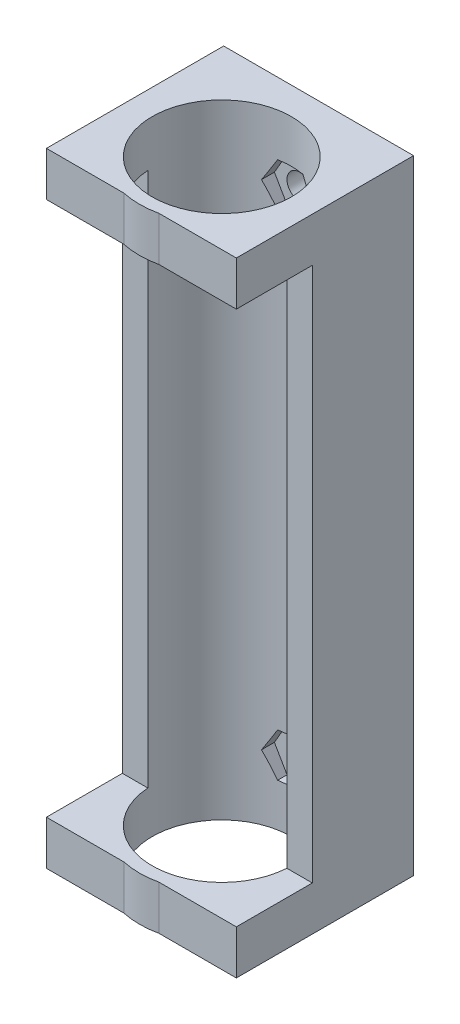
SolidWorks part; units mm, degrees
note: The reader was unsure of these and kept them because the rebuilt part matched: shared geometry of "Sketch2<2>", "Sketch2<3>", "Sketch1<6>", "Sketch1<7>".
material "ABS"
ref_plane "Front Plane" through (0, 0, 0) normal (0, 0, 1) x (1, 0, 0)
ref_plane "Top Plane" through (0, 0, 0) normal (0, 1, 0) x (1, 0, 0)
ref_plane "Right Plane" through (0, 0, 0) normal (1, 0, 0) x (0, 0, -1)
sketch "Sketch1" plane through (0, 0, 0) normal (0, 0, 1) x (1, 0, 0)
  line L0 (-315, -150.75) -> (-345, -150.75)
  line L1 (-315, -150.75) -> (-315, -249.25)
  line L2 (-345, -150.75) -> (-345, -249.25)
  line L3 (-315, -249.25) -> (-345, -249.25)
  line L4 (-343, -150.75) -> (-318.4975, -150.75) construction
  line L5 (-318.4975, -249.25) -> (-343, -249.25) construction
  line L7 (-326.0163, -161) -> (-328.0081, -157.55)
  line L8 (-328.0081, -157.55) -> (-331.9919, -157.55)
  line L9 (-331.9919, -157.55) -> (-333.9837, -161)
  line L10 (-333.9837, -161) -> (-331.9919, -164.45)
  line L11 (-331.9919, -164.45) -> (-328.0081, -164.45)
  line L12 (-328.0081, -164.45) -> (-326.0163, -161)
  line L13 (-333.9837, -239) -> (-331.9919, -242.45)
  line L14 (-331.9919, -242.45) -> (-328.0081, -242.45)
  line L15 (-328.0081, -242.45) -> (-326.0163, -239)
  line L16 (-326.0163, -239) -> (-328.0081, -235.55)
  line L17 (-328.0081, -235.55) -> (-331.9919, -235.55)
  line L18 (-331.9919, -235.55) -> (-333.9837, -239)
  circle A0 centre (-330, -161) radius 2 construction
  circle A1 centre (-330, -161) radius 2
  circle A2 centre (-330, -239) radius 2
  circle A3 centre (-330, -161) radius 3.45 construction
  circle A4 centre (-330, -239) radius 3.45 construction
  dimension "D1" = 15
  dimension "D2" = 15
  dimension "D3" = 0
  dimension "D4" = 0
  dimension "D5" = 6.9
  dimension "D6" = 6.9
sketch "Sketch2" plane through (0, -150.75, 0) normal (0, -1, 0) x (1, 0, 0)
  circle A0 centre (-330, 15.3006) radius 11
  circle A1 centre (-330, 15.3006) radius 13
  dimension "D1" = 22
  dimension "D2" = 26
extrude "Boss-Extrude3" add sketch "Sketch2" along normal up to surface (98.5 mm away)
extrude "Cut-Extrude2" cut sketch "Sketch2<2>" along normal offset from surface (84.5 mm away) 7 from offset 7
sketch "Sketch2<2>" plane through (0, -150.75, 0) normal (0, -1, 0) x (1, 0, 0) same geometry as "Sketch2"
extrude "Boss-Extrude5" add sketch "Sketch1" along normal blind 4 contours L3 L1 L0 L2 L18 L17 L16 L15 L14 L13 L12 L11 L10 L9 L8 L7 | L11 L12 L7 L8 L9 L10 A1 | L17 L18 L13 L14 L15 L16 A2
sketch "Sketch3" plane through (0, 0, 4) normal (0, 0, 1) x (1, 0, 0)
  line L0 (-315, -157.75) -> (-345, -157.75)
  line L1 (-315, -157.75) -> (-315, -242.25)
  line L2 (-345, -157.75) -> (-345, -242.25)
  line L3 (-315, -242.25) -> (-345, -242.25)
  line L4 (-315, -150.75) -> (-315, -249.25) construction
  line L5 (-345, -150.75) -> (-345, -249.25) construction
  line L6 (-341, -157.75) -> (-319, -157.75) construction
  line L7 (-319, -242.25) -> (-341, -242.25) construction
  line L8 (-315, -249.25) -> (-345, -249.25) construction
  line L9 (-345, -157.75) -> (-315, -157.75)
  line L10 (-345, -157.75) -> (-345, -150.75)
  line L11 (-345, -150.75) -> (-315, -150.75)
  line L12 (-315, -157.75) -> (-315, -150.75)
  line L13 (-345, -157.75) -> (-315, -150.75) construction
  line L14 (-345, -150.75) -> (-315, -157.75) construction
  line L15 (-345, -242.25) -> (-315, -242.25)
  line L16 (-345, -242.25) -> (-345, -249.25)
  line L17 (-345, -249.25) -> (-315, -249.25)
  line L18 (-315, -242.25) -> (-315, -249.25)
  line L19 (-345, -242.25) -> (-315, -249.25) construction
  line L20 (-345, -249.25) -> (-315, -242.25) construction
  line L21 (-336.4263, -150.75) -> (-345, -150.75) construction
  point P14 (-330, -154.25)
  point P18 (-330, -245.75)
  line M6 (-323.5737, -150.75) -> (-323.5737, -157.75)
  line M7 (-323.5737, -157.75) -> (-336.4263, -157.75)
  line M8 (-336.4263, -157.75) -> (-336.4263, -150.75)
  line M9 (-336.4263, -150.75) -> (-345, -150.75)
  line M10 (-345, -150.75) -> (-345, -249.25)
  line M11 (-345, -249.25) -> (-315, -249.25)
  line M12 (-315, -249.25) -> (-315, -150.75)
  line M13 (-315, -150.75) -> (-323.5737, -150.75)
extrude "Boss-Extrude8" add sketch "Sketch3" along normal blind 24 contours L0 M8 M9 M10 | L11 M8 M7 M6 | L3 M12 M10 M11 | L0 M12 M13 M6
sketch "Sketch4" plane through (0, -157.75, 0) normal (0, -1, 0) x (1, 0, 0)
  line L0 (-345, 16) -> (-315, 16)
  line L1 (-345, 28) -> (-345, 4) construction
  line L2 (-315, 28) -> (-315, 4) construction
  line L3 (-315, 16) -> (-315, 4)
  line L4 (-315, 4) -> (-345, 4)
  line L5 (-345, 4) -> (-345, 16)
extrude "Boss-Extrude9" add sketch "Sketch4" along normal up to surface (84.5 mm away)
extrude "Cut-Extrude3" cut sketch "Sketch2<3>" along normal through all
sketch "Sketch2<3>" plane through (0, -150.75, 0) normal (0, -1, 0) x (1, 0, 0) same geometry as "Sketch2"
extrude "Cut-Extrude4" cut sketch "Sketch1<6>" along normal blind 10 from offset 3 contours L11 L12 L7 L8 L9 L10 A1 | L17 L18 L13 L14 L15 L16 A2
sketch "Sketch1<6>" plane through (0, 0, 0) normal (0, 0, 1) x (1, 0, 0) same geometry as "Sketch1"
extrude "Cut-Extrude5" cut sketch "Sketch1<7>" along normal through all contours A1 | A2
sketch "Sketch1<7>" plane through (0, 0, 0) normal (0, 0, 1) x (1, 0, 0) same geometry as "Sketch1"
